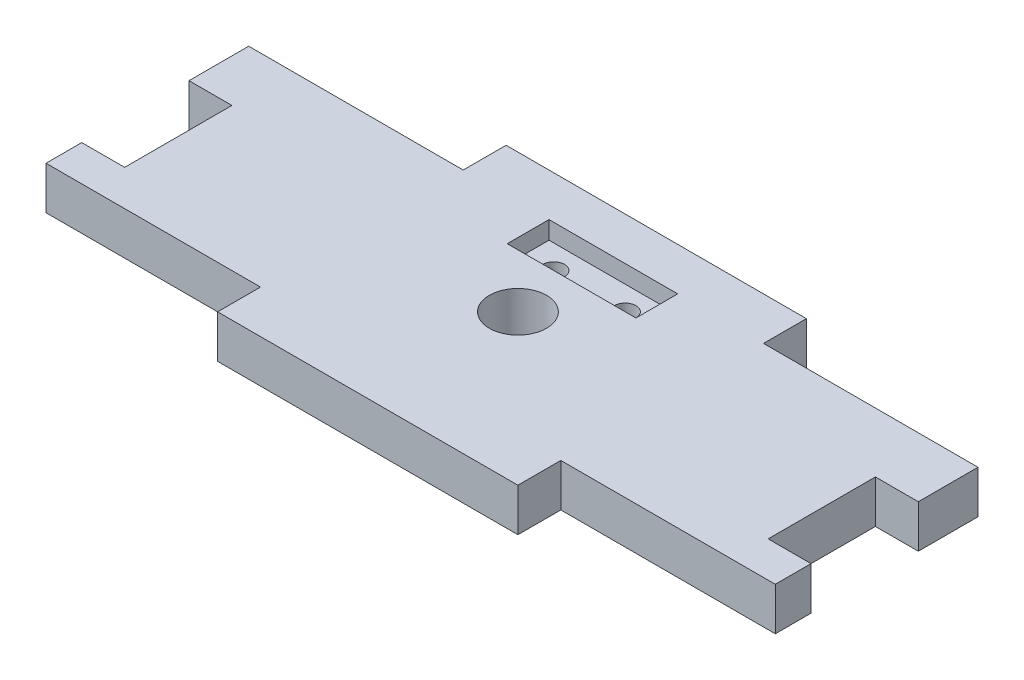
SolidWorks part; units mm, degrees
ref_plane "Front Plane" through (0, 0, 0) normal (0, 0, 1) x (1, 0, 0)
ref_plane "Top Plane" through (0, 0, 0) normal (0, 1, 0) x (1, 0, 0)
ref_plane "Right Plane" through (0, 0, 0) normal (1, 0, 0) x (0, 0, -1)
sketch "Sketch1" plane through (0, 0, 0) normal (0, 1, 0) x (1, 0, 0)
  line L1 (-50, -75) -> (50, -75)
  line L2 (-50, -75) -> (-50, 75)
  line L3 (-50, 75) -> (50, 75)
  line L4 (50, -75) -> (50, 75)
  line L5 (-50, -75) -> (50, 75) construction
  line L6 (-50, 75) -> (50, -75) construction
  point P0 (0, 0)
  dimension "D1" = 100
  dimension "D2" = 150
extrude "Boss-Extrude1" add sketch "Sketch1" along normal blind 150
sketch "Sketch13" plane through (50, 0, 0) normal (1, 0, 0) x (0, 0, -1)
  line L0 (-45, 40) -> (20, 0)
  line L1 (-75, 0) -> (-45, 0)
  line L2 (-75, 0) -> (-75, 40)
  line L3 (-75, 40) -> (-45, 40)
  line L5 (-75, 0) -> (75, 0) construction
  line L8 (-45, 0) -> (20, 0)
  dimension "D1" = 30
  dimension "D2" = 40
  dimension "D3" = 55
extrude "Cut-Extrude7" cut sketch "Sketch13" against normal up to next
shell "Shell1" thickness 6 removed face at (0, 150, 0)
sketch "Sketch3" plane through (0, 0, 0) normal (0, -1, 0) x (1, 0, 0)
  line L1 (50, 45) -> (50, 75) construction
  circle A0 centre (-1, 59.9917) radius 4
  circle A1 centre (-6, 49.9917) radius 1.5
  circle A2 centre (4, 49.9917) radius 1.5
  dimension "D3" = 8
  dimension "D4" = 3
  dimension "D5" = 10
  dimension "D7" = 10
  dimension "D8" = 5
  dimension "D1" = 60
  dimension "D2" = 51
extrude "Cut-Extrude2" cut sketch "Sketch3" against normal through all both and the other way through all
sketch "Sketch5" plane through (0, 0, 75) normal (0, 0, 1) x (1, 0, 0)
  line L0 (50, 150) -> (50, 40) construction
  line L1 (-25, 50) -> (25, 50)
  line L2 (-25, 50) -> (-25, 97)
  line L3 (-25, 97) -> (25, 97)
  line L4 (25, 50) -> (25, 97)
  line L5 (-25, 50) -> (25, 97) construction
  line L6 (-25, 97) -> (25, 50) construction
  line L7 (-50, 150) -> (50, 150) construction
  point P0 (0, 73.5)
  dimension "D1" = 50
  dimension "D2" = 47
  dimension "D3" = 50
  dimension "D4" = 76.5
extrude "Boss-Extrude3" add sketch "Sketch5" along normal blind 1
sketch "Sketch8" plane through (0, 0, 75) normal (0, 0, 1) x (1, 0, 0)
  line L0 (-50, 150) -> (-50, 40) construction
  line L1 (-25, 100) -> (25, 100)
  line L2 (-25, 100) -> (-25, 139)
  line L3 (-25, 139) -> (25, 139)
  line L4 (25, 100) -> (25, 139)
  line L5 (-25, 100) -> (25, 139) construction
  line L6 (-25, 139) -> (25, 100) construction
  line L7 (-50, 150) -> (50, 150) construction
  point P0 (0, 119.5)
  dimension "D1" = 50
  dimension "D2" = 39
  dimension "D3" = 50
  dimension "D4" = 50
extrude "Cut-Extrude3" cut sketch "Sketch8" against normal up to next
sketch "Sketch18" plane through (0, 0, 69) normal (0, 0, -1) x (-1, 0, 0)
  line L0 (-25, 139) -> (25, 139) construction
  line L1 (30, 99) -> (-26, 99)
  line L2 (30, 99) -> (30, 140)
  line L3 (30, 140) -> (-26, 140)
  line L4 (-26, 99) -> (-26, 140)
  line L6 (-25, 100) -> (-25, 139) construction
  line L7 (25, 139) -> (25, 100) construction
  dimension "D1" = 1
  dimension "D2" = 41
  dimension "D3" = 1
  dimension "D4" = 5
extrude "Cut-Extrude9" cut sketch "Sketch18" against normal blind 2
sketch "Sketch20" plane through (0, 0, 76) normal (0, 0, 1) x (1, 0, 0)
  line L0 (25, 97) -> (-25, 97) construction
  line L1 (-23, 96) -> (23, 96)
  line L2 (-23, 96) -> (-23, 51)
  line L3 (-23, 51) -> (23, 51)
  line L4 (23, 96) -> (23, 51)
  line L5 (-25, 50) -> (25, 50) construction
  line L6 (25, 50) -> (25, 97) construction
  line L7 (-25, 97) -> (-25, 50) construction
  dimension "D1" = 1
  dimension "D2" = 1
  dimension "D3" = 2
  dimension "D4" = 2
extrude "Cut-Extrude10" cut sketch "Sketch20" against normal blind 15 from offset 4 offset against normal yes
sketch "Sketch21" plane through (0, 46, 0) normal (0, 1, 0) x (1, 0, 0)
  line L1 (8, -52.4917) -> (-10, -52.4917)
  line L2 (8, -52.4917) -> (8, -37.4917)
  line L3 (8, -37.4917) -> (-10, -37.4917)
  line L4 (-10, -52.4917) -> (-10, -37.4917)
  circle A0 centre (4, -49.9917) radius 1.5 construction
  circle A1 centre (-6, -49.9917) radius 1.5 construction
  dimension "D3" = 4
  dimension "D1" = 4
  dimension "D2" = 2.5
  dimension "D4" = 15
extrude "Cut-Extrude11" cut sketch "Sketch21" against normal blind 2.5
sketch "Sketch22" plane through (-44, 0, 0) normal (1, 0, 0) x (0, 0, -1)
  line L0 (69, 150) -> (-69, 150) construction
  line L5 (69, 150) -> (69, 6) construction
  line L7 (-43.3017, 46) -> (21.6983, 6) construction
  line L8 (9, 150) -> (9, 13.8143)
  line L11 (9, 150) -> (4, 150)
  line L14 (4, 150) -> (4, 16.8912)
  line L15 (4, 16.8912) -> (9, 13.8143)
  dimension "D1" = 60
  dimension "D3" = 5
extrude "Boss-Extrude6" add sketch "Sketch22" along normal blind 5
mirror "Mirror2" about plane through (0, 0, 0) normal (1, 0, 0) of "Boss-Extrude6"
sketch "Sketch23" plane through (-44, 0, 0) normal (1, 0, 0) x (0, 0, -1)
  line L0 (15, 150) -> (20, 150)
  line L1 (69, 150) -> (9, 150) construction
  line L3 (20, 150) -> (20, 7.0451)
  line L4 (20, 7.0451) -> (15, 10.122)
  line L6 (9, 13.8143) -> (9, 150) construction
  line L7 (15, 150) -> (15, 10.122)
  line L8 (9, 13.8143) -> (21.6983, 6) construction
  dimension "D1" = 6
  dimension "D2" = 5
extrude "Boss-Extrude7" add sketch "Sketch23" along normal up to next
sketch "Sketch24" plane through (-44, 0, 0) normal (1, 0, 0) x (0, 0, -1)
  line L0 (69, 150) -> (69, 6) construction
  line L1 (69, 135) -> (66, 135)
  line L2 (69, 135) -> (69, 105)
  line L3 (69, 105) -> (66, 105)
  line L4 (66, 135) -> (66, 105)
  line L5 (69, 150) -> (20, 150) construction
  line L6 (69, 6) -> (21.6983, 6) construction
  line L7 (69, 21) -> (66, 21)
  line L8 (69, 21) -> (69, 51)
  line L9 (69, 51) -> (66, 51)
  line L10 (66, 21) -> (66, 51)
  dimension "D1" = 15
  dimension "D2" = 30
  dimension "D3" = 3
  dimension "D4" = 15
extrude "Cut-Extrude12" cut sketch "Sketch24" against normal through all both and the other way through all
sketch "Sketch28" plane through (0, 0, 76) normal (0, 0, 1) x (1, 0, 0)
  line L0 (-25, 73.5) -> (25, 73.5) construction
  line L1 (-25, 97) -> (-25, 50) construction
  line L2 (25, 50) -> (25, 97) construction
  line L3 (-25, 77.511) -> (25, 77.511) construction
  text T0 "SCAN\r\nHERE" font "Impact" height 10
extrude "Cut-Extrude14" cut sketch "Sketch28" against normal blind 1
sketch "Sketch30" plane through (0, 0, -75) normal (0, 0, -1) x (-1, 0, 0)
  text T0 "IBE VAN DE VEIRE\r\nSTEF GIELEN" font "Comic Sans MS" height 5
extrude "Cut-Extrude16" cut sketch "Sketch30" against normal blind 1
sketch "Sketch32" plane through (0, 150, 0) normal (0, 1, 0) x (1, 0, 0)
  line L0 (-50, 75) -> (-50, -75) construction
  line L1 (50, 75) -> (-50, 75) construction
  line L2 (-50, -75) -> (50, -75) construction
  line L3 (50, -75) -> (50, 75) construction
  circle A0 centre (-47, 72) radius 1.225
  circle A1 centre (-47, -72) radius 1.225
  circle A2 centre (47, -72) radius 1.225
  circle A3 centre (47, 72) radius 1.225
  dimension "D1" = 2.45
  dimension "D2" = 3
  dimension "D3" = 3
  dimension "D4" = 2.45
  dimension "D5" = 3
  dimension "D6" = 3
  dimension "D7" = 2.45
  dimension "D8" = 3
  dimension "D9" = 3
  dimension "D10" = 2.45
  dimension "D11" = 3
  dimension "D12" = 3
extrude "Cut-Extrude17" cut sketch "Sketch32" against normal blind 20
sketch "Sketch33" plane through (0, 150, 0) normal (0, 1, 0) x (1, 0, 0)
  line L1 (-44, 4) -> (44, 4)
  line L2 (-44, 4) -> (-44, 20)
  line L3 (-44, 20) -> (44, 20)
  line L4 (44, 4) -> (44, 20)
extrude "Cut-Extrude18" cut sketch "Sketch33" against normal blind 40
sketch "Sketch34" plane through (0, 150, 0) normal (0, 1, 0) x (1, 0, 0)
  line L0 (50, 75) -> (-50, 75) construction
  line L1 (-45, 75) -> (50, 75)
  line L2 (-45, 75) -> (-45, -75)
  line L3 (-45, -75) -> (50, -75)
  line L4 (50, 75) -> (50, -75)
sketch "Sketch36" plane through (0, 40, 0) normal (0, -1, 0) x (1, 0, 0)
  line L1 (-50, 45) -> (72.0124, 45)
  line L2 (-50, 45) -> (-50, -130.6741)
  line L3 (-50, -130.6741) -> (72.0124, -130.6741)
  line L4 (72.0124, 45) -> (72.0124, -130.6741)
extrude "Cut-Extrude19" cut sketch "Sketch36" against normal through all both and the other way through all
sketch "Sketch38" plane through (50, 0, 0) normal (1, 0, 0) x (0, 0, -1)
  line L0 (-75, 150) -> (-45, 150) construction
  line L1 (-75, 40) -> (-70, 40)
  line L2 (-75, 40) -> (-75, 150)
  line L3 (-75, 150) -> (-70, 150)
  line L4 (-70, 40) -> (-70, 150)
  dimension "D1" = 5
extrude "Cut-Extrude20" cut sketch "Sketch38" against normal through all both and the other way through all
sketch "Sketch40" plane through (44, 0, 0) normal (-1, 0, 0) x (0, 0, 1)
  line L1 (45, 46) -> (168.4963, 46)
  line L2 (45, 46) -> (45, 279.6174)
  line L3 (45, 279.6174) -> (168.4963, 279.6174)
  line L4 (168.4963, 46) -> (168.4963, 279.6174)
extrude "Cut-Extrude21" cut sketch "Sketch40" against normal through all both and the other way through all
sketch "Sketch42" plane through (-50, 0, 0) normal (-1, 0, 0) x (0, 0, 1)
  line L0 (70, 40) -> (70, 46) construction
  line L1 (70, 46) -> (45, 46)
  line L2 (70, 46) -> (70, 40)
  line L3 (70, 40) -> (45, 40)
  line L4 (45, 46) -> (45, 40)
  line L5 (45, 46) -> (70, 46) construction
  line L6 (70, 40) -> (45, 40) construction
  line L7 (45, 46) -> (45, 40) construction
extrude "Boss-Extrude9" add sketch "Sketch42" along normal blind 2
sketch "Sketch43" plane through (0, 0, 70) normal (0, 0, 1) x (1, 0, 0)
  line L0 (50, 46) -> (-52, 46) construction
  line L1 (-52, 46) -> (50, 46)
  line L2 (-52, 46) -> (-52, 40)
  line L3 (-52, 40) -> (50, 40)
  line L4 (50, 46) -> (50, 40)
  line L5 (-52, 40) -> (-52, 46) construction
  line L6 (-52, 40) -> (50, 40) construction
  line L7 (50, 46) -> (50, 40) construction
extrude "Boss-Extrude10" add sketch "Sketch43" along normal blind 11
sketch "Sketch44" plane through (0, 0, 81) normal (0, 0, 1) x (1, 0, 0)
  line L0 (50, 46) -> (-52, 46) construction
  line L1 (-52, 40) -> (-22, 40)
  line L2 (-52, 40) -> (-52, 46)
  line L3 (-52, 46) -> (-22, 46)
  line L4 (-22, 40) -> (-22, 46)
  dimension "D1" = 30
extrude "Cut-Extrude22" cut sketch "Sketch44" against normal blind 6
pattern_linear "LPattern1" count 3 spacing 72 along (1, 0, 0) of "Cut-Extrude22"
sketch "Sketch45" plane through (0, 0, 45) normal (0, 0, -1) x (-1, 0, 0)
  line L1 (-50, 40) -> (52, 40)
  line L2 (-50, 40) -> (-50, 46)
  line L3 (-50, 46) -> (52, 46)
  line L4 (52, 40) -> (52, 46)
extrude "Cut-Extrude23" cut sketch "Sketch45" against normal blind 1.65
sketch "Sketch46" plane through (0, 0, 46.65) normal (0, 0, -1) x (-1, 0, 0)
  line L0 (-50, 40) -> (52, 40) construction
  line L1 (-20, 40) -> (22, 40)
  line L2 (-20, 40) -> (-20, 46)
  line L3 (-20, 46) -> (22, 46)
  line L4 (22, 40) -> (22, 46)
  line L5 (52, 46) -> (10, 46) construction
  line L6 (52, 40) -> (52, 46) construction
  line L7 (-50, 46) -> (-50, 40) construction
  dimension "D1" = 30
  dimension "D2" = 30
extrude "Boss-Extrude11" add sketch "Sketch46" along normal blind 6
sketch "Sketch48" plane through (50, 0, 0) normal (1, 0, 0) x (0, 0, -1)
  line L0 (-46.65, 46) -> (-75, 46) construction
  line L1 (-55, 46) -> (-70, 46)
  line L2 (-55, 46) -> (-55, 40)
  line L3 (-55, 40) -> (-70, 40)
  line L4 (-70, 46) -> (-70, 40)
  line L5 (-46.65, 40) -> (-75, 40) construction
  line L6 (-75, 40) -> (-75, 46) construction
  dimension "D1" = 5
  dimension "D2" = 15
extrude "Cut-Extrude24" cut sketch "Sketch48" against normal blind 6
ref_plane "Plane1" through (-1, 0, 0) normal (1, 0, 0) x (0, 0, -1)
mirror "Mirror3" about plane through (-1, 0, 0) normal (1, 0, 0) of "Cut-Extrude24"
